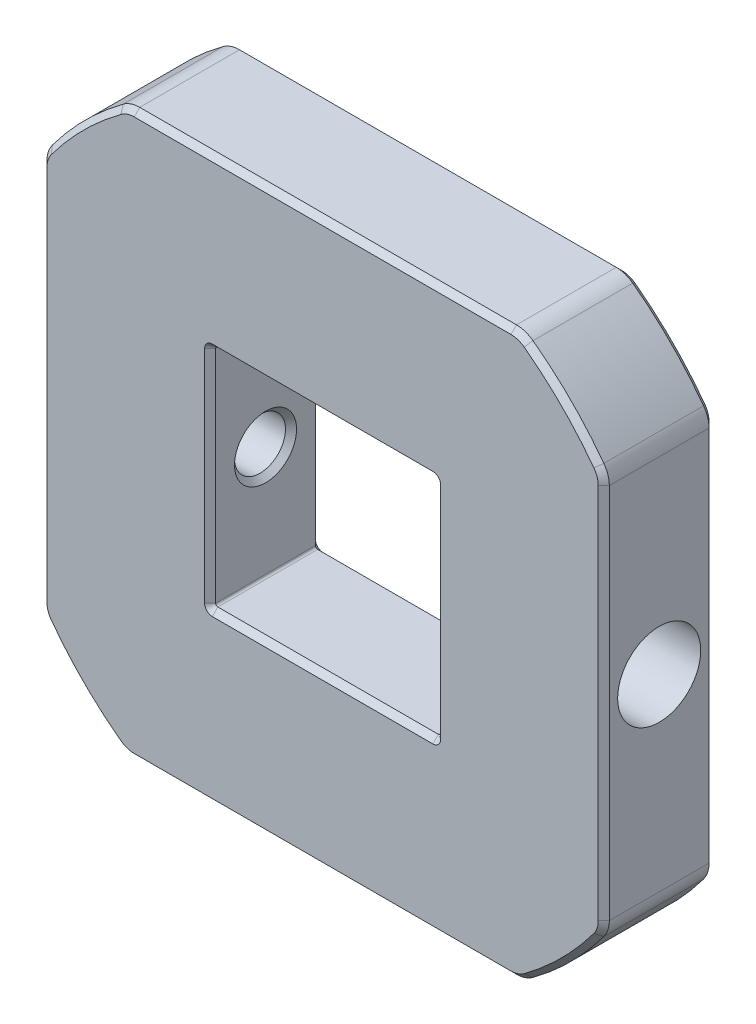
SolidWorks part; units mm, degrees
ref_plane "Front" through (0, 0, 0) normal (0, 0, 1) x (1, 0, 0)
ref_plane "Top" through (0, 0, 0) normal (0, 1, 0) x (1, 0, 0)
ref_plane "Right" through (0, 0, 0) normal (1, 0, 0) x (0, 0, -1)
sketch "Skizze1" plane through (0, 0, 0) normal (0, 0, 1) x (1, 0, 0)
  line L0 (17.8076, 25.375) -> (-17.8076, 25.375)
  line L1 (-10.15, -10.15) -> (10.15, -10.15)
  line L2 (-10.15, -10.15) -> (-10.15, 10.15)
  line L3 (-10.15, 10.15) -> (10.15, 10.15)
  line L4 (10.15, -10.15) -> (10.15, 10.15)
  line L5 (-10.15, -10.15) -> (10.15, 10.15) construction
  line L6 (-10.15, 10.15) -> (10.15, -10.15) construction
  line L7 (25.375, 17.8076) -> (25.375, -17.8076)
  line L8 (-17.8076, -25.375) -> (17.8076, -25.375)
  line L9 (-25.375, -17.8076) -> (-25.375, 17.8076)
  arc A0 (-25.375, -17.8076) -> (-17.8076, -25.375) centre (0, 0) ccw
  arc A1 (-17.8076, 25.375) -> (-25.375, 17.8076) centre (0, 0) ccw
  arc A2 (25.375, 17.8076) -> (17.8076, 25.375) centre (0, 0) ccw
  arc A3 (17.8076, -25.375) -> (25.375, -17.8076) centre (0, 0) ccw
  dimension "D1" = 62
  dimension "D2" = 20.3
  dimension "D3" = 50.75
extrude "Aufsatz-Linear austragen1" add sketch "Skizze1" along normal blind 10
fillet "Verrundung1" radius 0.2 4 edges at (10.15, -10.15, 5) (-10.15, -10.15, 5) (-10.15, 10.15, 5) (10.15, 10.15, 5)
fillet "Verrundung2" radius 2.5 8 edges at (17.8076, 25.375, 5) (25.375, 17.8076, 5) (25.375, -17.8076, 5) (17.8076, -25.375, 5) (-17.8076, -25.375, 5) (-25.375, -17.8076, 5) (-25.375, 17.8076, 5) (-17.8076, 25.375, 5)
sketch "Skizze2" plane through (25.375, 0, 0) normal (1, 0, 0) x (0, 0, -1)
  line L0 (0, 0) -> (-10, 0) construction
  line L1 (-10, -16.9995) -> (-10, 16.9995) construction
  circle A0 centre (-5, 0) radius 2.3
  dimension "D1" = 4.6
extrude "Schnitt-Linear austragen1" cut sketch "Skizze2" against normal through all
sketch "Sketch1" plane through (-25.375, 0, 0) normal (-1, 0, 0) x (0, 0, 1)
  circle A0 centre (5, 0) radius 3.75
  dimension "D1" = 7.5
extrude "Cut-Extrude1" cut sketch "Sketch1" against normal offset from surface (8.025 mm away) 7.2 up to face at (-10.15, 0, 2.7)
extrude "Cut-Extrude2" cut sketch "Sketch1<2>" along normal offset from surface (8.025 mm away) 7.2 from surface up to face at (10.15, 0, 7.3) starting at face at (25.375, 2.3, 5)
sketch "Sketch1<2>" plane through (-25.375, 0, 0) normal (-1, 0, 0) x (0, 0, 1) same geometry as "Sketch1"
chamfer "Fase2" distance 0.5 angle 45 52 edges at (10.15, 0, 7.3) (-10.15, 0, 2.7) (-10.0914, 10.0914, 10) (-10.15, 0, 10) (-10.0914, -10.0914, 10) (0, -10.15, 10) (10.0914, -10.0914, 10) (10.15, 0, 10) (10.0914, 10.0914, 10) (0, 10.15, 10) (25.2484, 17.7849, 10) (25.375, 0, 10) (25.2484, -17.7849, 10) (21.9203, -21.9203, 10) (17.7849, -25.2484, 10) (0, -25.375, 10) (-17.7849, -25.2484, 10) (-21.9203, -21.9203, 10) (-25.2484, -17.7849, 10) (-25.375, 0, 10) (-25.2484, 17.7849, 10) (-21.9203, 21.9203, 10) (-17.7849, 25.2484, 10) (0, 25.375, 10) (17.7849, 25.2484, 10) (21.9203, 21.9203, 10) (-10.0914, -10.0914, 0) (-10.15, 0, 0) (-10.0914, 10.0914, 0) (0, 10.15, 0) (10.0914, 10.0914, 0) (10.15, 0, 0) (10.0914, -10.0914, 0) (0, -10.15, 0) (-17.7849, 25.2484, 0) (-21.9203, 21.9203, 0) (-25.2484, 17.7849, 0) (-25.375, 0, 0) (-25.2484, -17.7849, 0) (-21.9203, -21.9203, 0) (-17.7849, -25.2484, 0) (0, -25.375, 0) (17.7849, -25.2484, 0) (21.9203, -21.9203, 0) (25.2484, -17.7849, 0) (25.375, 0, 0) (25.2484, 17.7849, 0) (21.9203, 21.9203, 0) (17.7849, 25.2484, 0) (0, 25.375, 0) (17.35, 0, 7.3) (-17.35, 0, 2.7)
